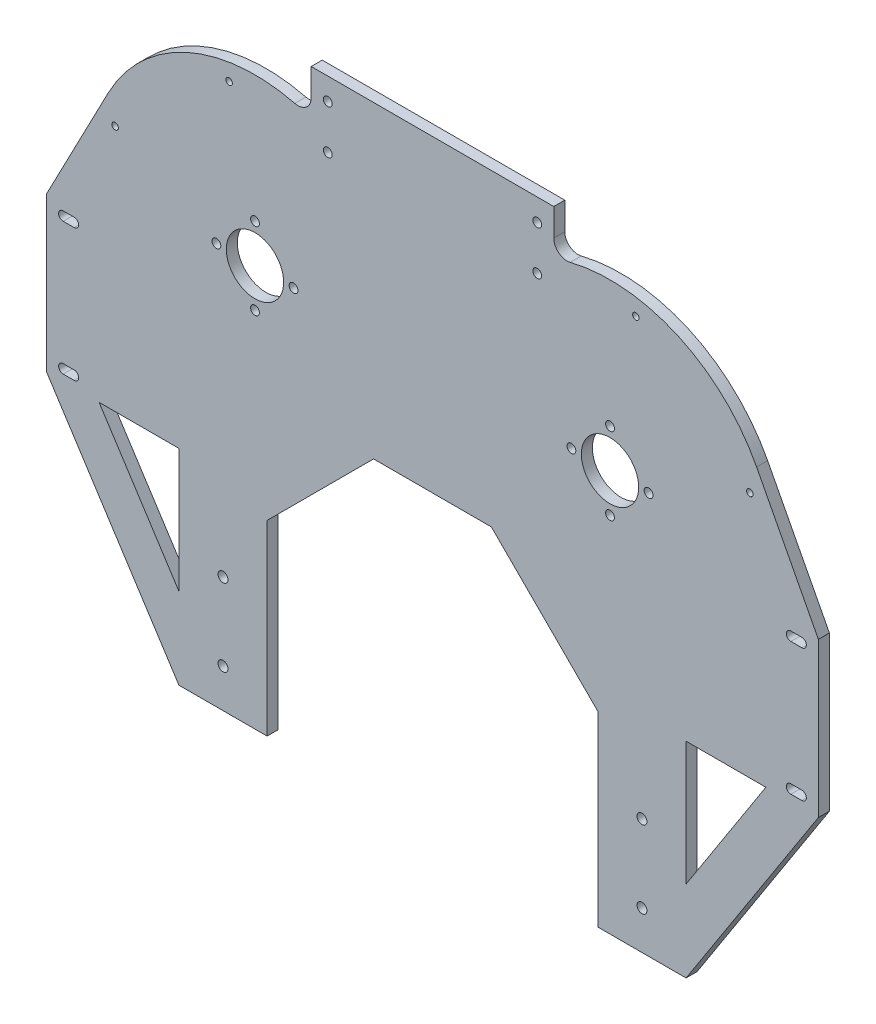
SolidWorks part; units mm, degrees
ref_plane "Front Plane" through (0, 0, 0) normal (0, 0, 1) x (1, 0, 0)
ref_plane "Top Plane" through (0, 0, 0) normal (0, 1, 0) x (1, 0, 0)
ref_plane "Right Plane" through (0, 0, 0) normal (1, 0, 0) x (0, 0, -1)
sketch "Sketch1" plane through (0, 0, 0) normal (0, 0, 1) x (1, 0, 0)
  line L1 (-100, -75) -> (100, -75)
  line L2 (-100, -75) -> (-100, 75)
  line L3 (-100, 75) -> (100, 75)
  line L4 (100, -75) -> (100, 75)
  line L5 (-100, -75) -> (100, 75) construction
  line L6 (-100, 75) -> (100, -75) construction
  line L8 (-47.5, 40) -> (47.5, 40) construction
  line L9 (0, 75) -> (0, -75) construction
  line L10 (-27, -44) -> (27, -44) construction
  line L11 (-27, -44) -> (-27, 28) construction
  line L12 (-27, 28) -> (27, 28) construction
  line L13 (27, -44) -> (27, 28) construction
  line L14 (-27, -44) -> (27, 28) construction
  line L15 (-27, 28) -> (27, -44) construction
  line L23 (-55, 70) -> (55, 70)
  line L24 (-55, 70) -> (-55, -70)
  line L25 (-55, -70) -> (55, -70)
  line L26 (55, 70) -> (55, -70)
  line L27 (-55, 70) -> (55, -70) construction
  line L28 (-55, -70) -> (55, 70) construction
  line L29 (-32.5, 70) -> (32.5, 70) construction
  line L30 (-32.5, 70) -> (-32.5, 55) construction
  line L31 (-32.5, 55) -> (32.5, 55) construction
  line L32 (32.5, 70) -> (32.5, 55) construction
  line L33 (-32.5, 70) -> (32.5, 55) construction
  line L34 (-32.5, 55) -> (32.5, 70) construction
  circle A2 centre (-47.5, 40) radius 2
  circle A3 centre (47.5, 40) radius 2
  circle A4 centre (-27, 28) radius 2 construction
  circle A5 centre (27, 28) radius 2 construction
  circle A6 centre (27, -44) radius 2 construction
  circle A7 centre (-27, -44) radius 2 construction
  circle A8 centre (-47.5, 60) radius 2
  circle A10 centre (47.5, 60) radius 2
  point P0 (0, 0)
  point P15 (0, 40)
  point P18 (0, -8)
  point P56 (0, 0)
  point P63 (0, 62.5)
  dimension "D3" = 4
  dimension "D4" = 20
  dimension "D5" = 4
  dimension "D8" = 4
  dimension "D1" = 150
  dimension "D2" = 200
  dimension "D6" = 72
  dimension "D7" = 54
  dimension "D14" = 30
  dimension "D15" = 140
  dimension "D16" = 110
  dimension "D17" = 95
  dimension "D18" = 12
  dimension "D19" = 15
  dimension "D20" = 65
extrude "Boss-Extrude1" add sketch "Sketch1" along normal blind 5 contours L23 L32 L31 L30 L24 L25 L26 A7 A6 A5 A4 A3 A2 region at (0, -0.1637, 0)
sketch "Sketch2" plane through (0, 0, 0) normal (0, 0, 1) x (1, 0, 0)
  line L0 (-55, -70) -> (-100.8579, -115.8579) construction
  line L1 (-55, 70) -> (-55, -70) construction
  line L2 (-55, -41.7157) -> (-115, -101.7157)
  line L3 (-26.7157, -70) -> (-86.7157, -130)
  line L4 (-55, -70) -> (55, -70) construction
  line L5 (-115, -101.7157) -> (-86.7157, -130)
  line L6 (-115, -101.7157) -> (-115, -203)
  line L7 (-75, -118.2843) -> (-75, -203)
  line L8 (-75, -203) -> (-115, -203)
  line L9 (0, 75) -> (0, -75) construction
  line L10 (-55, -41.7157) -> (-26.7157, -70)
  line L11 (-55, 70) -> (-55, -70) construction
  line L12 (-115, -203) -> (-75, -203) construction
  circle A0 centre (-95, -150.5) radius 2.25
  circle A1 centre (-95, -185.5) radius 2.25
  circle A2 centre (-95, -150.5) radius 2.25 construction
  circle A4 centre (-95, -185.5) radius 2.25 construction
  dimension "D1" = 135
  dimension "D2" = 40
  dimension "D3" = 40
  dimension "D4" = 75
  dimension "D5" = 0
extrude "Boss-Extrude2" add sketch "Sketch2" along normal blind 5 contours L8 L7 L3 L5 L6 | L10 L2 L5 L3 region at (-70.8579, -85.8579, 0) region at (-95.9307, -160.1869, 0)
mirror "Mirror1" about plane through (0, 0, 0) normal (1, 0, 0) of "Boss-Extrude2"
sketch "Sketch3" plane through (0, 0, 5) normal (0, 0, 1) x (1, 0, 0)
  line L0 (0, 31.3301) -> (0, 52.1198) construction
  line L1 (-80.5, -21) -> (-92.2213, 45.4745) construction
  line L2 (-80.5, -21) -> (80.5, -21) construction
  line L3 (-80.5, -21) -> (-148, -21) construction
  line L4 (-80.5, -21) -> (-143.9293, 2.0864) construction
  circle A0 centre (-80.5, -21) radius 75
  circle A1 centre (-80.5, -3.5) radius 2
  circle A2 centre (80.5, -21) radius 75
  circle A3 centre (-80.5, -21) radius 60
  circle A4 centre (80.5, -21) radius 60
  circle A5 centre (-47.5, 40) radius 2 construction
  circle A6 centre (-47.5, 40) radius 2
  circle A7 centre (47.5, 40) radius 2
  circle A8 centre (-63, -21) radius 2
  circle A9 centre (-80.5, -38.5) radius 2
  circle A10 centre (-98, -21) radius 2
  circle A11 centre (98, -21) radius 2
  circle A12 centre (80.5, -38.5) radius 2
  circle A13 centre (63, -21) radius 2
  circle A14 centre (80.5, -3.5) radius 2
  circle A15 centre (-80.5, -21) radius 13
  circle A16 centre (80.5, -21) radius 13
  circle A17 centre (-92.2213, 45.4745) radius 1.4732
  circle A18 centre (-143.9293, 2.0864) radius 1.4732
  circle A19 centre (-80.5, -21) radius 67.5 construction
  circle A20 centre (92.2213, 45.4745) radius 1.4732
  circle A21 centre (143.9293, 2.0864) radius 1.4732
  point P28 (-80.5, -21)
  line M3 (115, -101.7157) -> (55, -41.7157)
  line M4 (55, -41.7157) -> (55, 70)
  line M6 (-55, 70) -> (-55, -41.7157)
  line M7 (-55, -41.7157) -> (-115, -101.7157)
  line M11 (-75, -118.2843) -> (-26.7157, -70)
  line M12 (-26.7157, -70) -> (26.7157, -70)
  line M13 (26.7157, -70) -> (75, -118.2843)
  circle M17 centre (-47.5, 40) radius 2
  circle M18 centre (47.5, 40) radius 2
  dimension "D1" = 161
  dimension "D2" = 150
  dimension "D3" = 61
  dimension "D4" = 120
  dimension "D5" = 4
  dimension "D7" = 35
  dimension "D8" = 26
  dimension "D9" = 7.5
  dimension "D10" = 2.9464
  dimension "D6" = 4
  dimension "D11" = 80
  dimension "D12" = 20
extrude "Boss-Extrude3" add sketch "Sketch3" against normal up to surface (5 mm away) contours A3 M6 M7 | A3 A0 M6 M7 | A3 A0 M7 M11 M12 M6 M17 | A3 M7 M6 | A4 M3 M4 | A4 M4 M3 | A4 A2 M4 M3 | A4 A2 M3 M4 M12 M13 M18 region at (-11.8554, -46.5242, 5) region at (9.6495, -2.4591, 5) region at (-56.7712, 41.4218, 5) region at (-96.2806, -16.4848, 5) region at (-46.5969, -30.7004, 5) region at (122.5668, 38.9404, 5) region at (46.5969, -30.7004, 5) region at (96.2806, -16.4848, 5) up to face at (0, -95.388, 0)
sketch "Sketch4" plane through (0, 0, 5) normal (0, 0, 1) x (1, 0, 0)
  line L0 (-175, -75) -> (-100, -75) construction
  line L1 (-100, -40) -> (-153.0534, -40)
  line L2 (-100, -40) -> (-100, -110)
  line L3 (-100, -110) -> (-115, -110) construction
  line L4 (-175, -40) -> (-175, -110)
  line L5 (-100, -40) -> (-175, -110) construction
  line L6 (-100, -110) -> (-175, -40) construction
  line L7 (-175, -110) -> (-115, -203)
  line L8 (-151.1989, -110) -> (-115, -166.1083)
  line L9 (-115, -101.7157) -> (-115, -203) construction
  line L10 (-115, -166.1083) -> (-115, -203)
  line L11 (-175, -40) -> (-146.9976, 13.6853)
  line L12 (-153.0534, -40) -> (-175, -40)
  line L13 (-100, -110) -> (-115, -110) construction
  line L14 (-100, -110) -> (-100, -101.7157)
  line L15 (-100, -101.7157) -> (-115, -101.7157)
  line L16 (-115, -110) -> (-115, -101.7157)
  line L17 (-100, -110) -> (-115, -101.7157) construction
  line L18 (-100, -101.7157) -> (-115, -110) construction
  line L19 (-151.1989, -110) -> (-175, -110) construction
  line L20 (-115, -110) -> (-151.1989, -110)
  line L21 (-165, -75) -> (-165, -40) construction
  line L22 (-162.5, -45) -> (-167.5, -45) construction
  line L23 (-162.5, -47.05) -> (-167.5, -47.05)
  line L24 (-162.5, -42.95) -> (-167.5, -42.95)
  line L25 (-162.5, -105) -> (-167.5, -105) construction
  line L26 (-162.5, -102.95) -> (-167.5, -102.95)
  line L27 (-162.5, -107.05) -> (-167.5, -107.05)
  arc A0 (-55, 49.5319) -> (-105.1261, -91.8418) centre (-80.5, -21) ccw construction
  arc A1 (-146.9976, 13.6853) -> (-153.0534, -40) centre (-80.5, -21) ccw
  circle A2 centre (-165, -45) radius 2.05 construction
  arc A3 (-162.5, -47.05) -> (-162.5, -42.95) centre (-162.5, -45) ccw
  arc A4 (-167.5, -42.95) -> (-167.5, -47.05) centre (-167.5, -45) ccw
  arc A5 (-162.5, -102.95) -> (-162.5, -107.05) centre (-162.5, -105) cw
  arc A6 (-167.5, -107.05) -> (-167.5, -102.95) centre (-167.5, -105) cw
  point P4 (-137.5, -75)
  point P23 (-107.5, -105.8579)
  point P32 (-165, -45)
  point P40 (-165, -105)
  arc M12 (-55, 49.5319) -> (-105.1261, -91.8418) centre (-80.5, -21) ccw
  line M13 (-105.1261, -91.8418) -> (-115, -101.7157)
  line M14 (-115, -101.7157) -> (-115, -203)
  circle M41 centre (-143.9293, 2.0864) radius 1.4732
  dimension "D7" = 4.1
  dimension "D8" = 2.05
  dimension "D1" = 40
  dimension "D2" = 100
  dimension "D3" = 70
  dimension "D4" = 75
  dimension "D5" = 20
  dimension "D6" = 10
  dimension "D9" = 5
  dimension "D10" = 5
extrude "Boss-Extrude5" add sketch "Sketch4" against normal up to surface (5 mm away) contours L20 L16 L12 L4 L7 L8 A4 L24 A3 L23 L27 A6 L26 A5 M13 M12 M14 | L15 L14 L2 L1 M12 M13 M41 | L12 L11 M12 region at (-120.1023, -62.6792, 5) region at (-145.9871, -106.3764, 5) region at (-161.1873, -26.2241, 5) up to face at (0, -80.3864, 0)
mirror "Mirror2" about plane through (0, 0, 0) normal (1, 0, 0) of "Boss-Extrude5"
fillet "Fillet1" radius 6 2 edges at (55, 49.5319, 2.5) (-55, 49.5319, 2.5)
